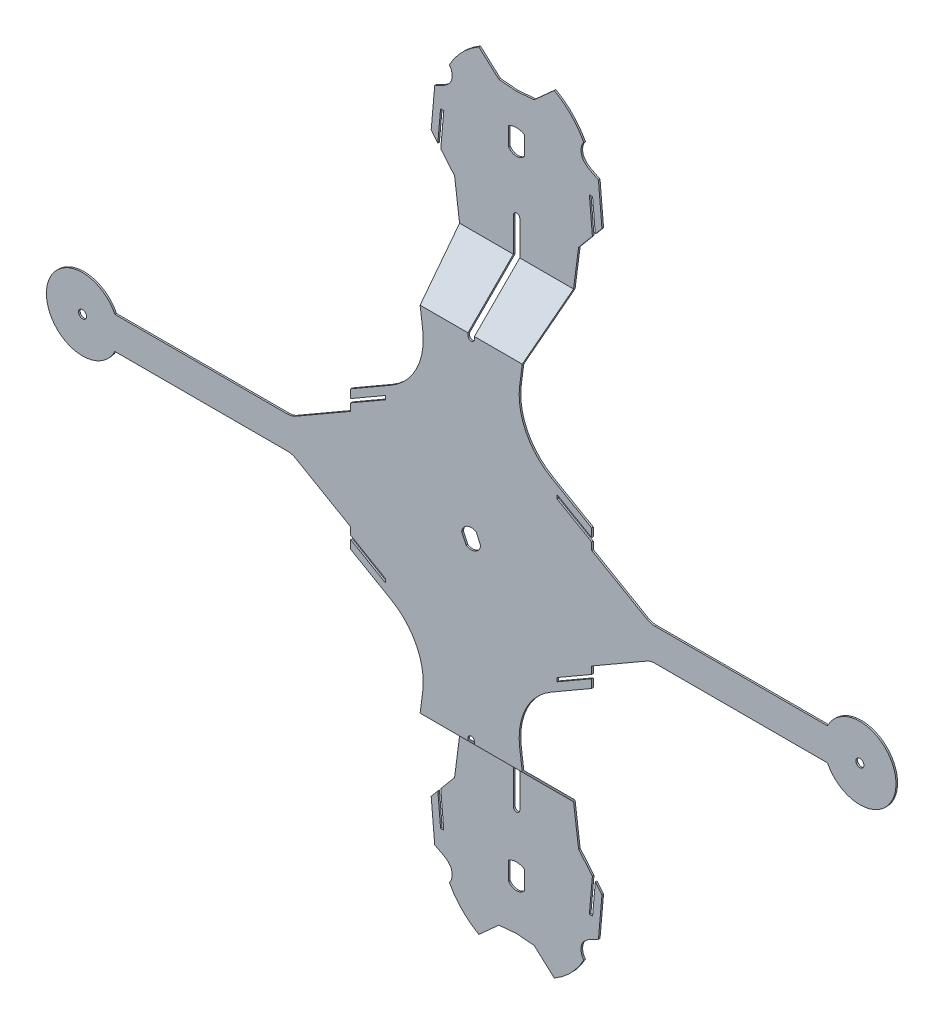
SolidWorks part; units mm, degrees
ref_plane "Alzado" through (0, 0, 0) normal (0, 0, 1) x (1, 0, 0)
ref_plane "Planta" through (0, 0, 0) normal (0, 1, 0) x (1, 0, 0)
ref_plane "Vista lateral" through (0, 0, 0) normal (1, 0, 0) x (0, 0, -1)
sketch "Croquis1" plane through (0, 0, 0) normal (1, 0, 0) x (0, 0, -1)
  line L2 (-31.6304, 0) -> (31.6304, 0) construction
  line L13 (17.5, 0) -> (17.5, 110)
  line L14 (17.5, 110) -> (45.7489, 138.2489)
  line L15 (45.7489, 138.2489) -> (45.7489, 248)
  line L16 (18.5, 0) -> (18.5, 109.5858)
  line L17 (18.5, 109.5858) -> (46.7489, 137.8347)
  line L18 (46.7489, 137.8347) -> (46.7489, 248)
  line L19 (45.7489, 248) -> (46.7489, 248)
  line L20 (45.7489, -248) -> (46.7489, -248)
  line L21 (46.7489, -137.8347) -> (46.7489, -248)
  line L22 (18.5, -109.5858) -> (46.7489, -137.8347)
  line L23 (18.5, 0) -> (18.5, -109.5858)
  line L24 (45.7489, -138.2489) -> (45.7489, -248)
  line L25 (17.5, -110) -> (45.7489, -138.2489)
  line L26 (17.5, 0) -> (17.5, -110)
  point P3 (0, 0)
  dimension "D1" = 17.5
  dimension "D2" = 110
  dimension "D3" = 45
  dimension "D4" = 39.95
  dimension "D5" = 496
  dimension "D6" = 1
extrude "Saliente-Extruir1" add sketch "Croquis1" along normal mid plane 542
sketch "Croquis5" plane through (0, 0, 0) normal (0, 0, 1) x (1, 0, 0)
  line L0 (-923.9507, 561.734) -> (-241.388, 573.6482) construction
sketch "Croquis2" plane through (0, 0, 0) normal (0, 0, 1) x (1, 0, 0)
  line L1 (0, 277.0309) -> (0, -277.0309) construction
  line L9 (-300.4496, 0) -> (300.4496, 0) construction
  line L10 (0, 108.5) -> (0, 159.5) construction
  line L11 (-2, 108.5) -> (-2, 159.5)
  line L12 (2, 108.5) -> (2, 159.5)
  line L13 (-30, 152) -> (-47.205, 172.5041) construction
  line L14 (-53.1684, 179.6111) -> (-50.9701, 204.7381)
  line L15 (-23.5, 239.2795) -> (-11, 228.0419)
  line L34 (-11, 228.0419) -> (0, 227.0795)
  line L35 (-49.0231, 174.6708) -> (-47.3316, 194.0041)
  line L36 (-47.3316, 194.0041) -> (-45.324, 194.0041)
  line L37 (-45.324, 194.0041) -> (-47.205, 172.5041)
  line L38 (-49.0231, 174.6708) -> (-53.1684, 179.6111)
  line L45 (-38.6025, 162.2521) -> (-26.75, 71.1584)
  line L79 (0, 86.6025) -> (-75, 43.3013) construction
  line L83 (-75, 43.3013) -> (-75, 38.0358)
  line L84 (-75, -43.3013) -> (0, -86.6025) construction
  line L85 (0, -86.6025) -> (75, -43.3013) construction
  line L86 (75, -43.3013) -> (75, 43.3013) construction
  line L87 (75, 43.3013) -> (0, 86.6025) construction
  line L88 (-38.6025, 162.2521) -> (-47.205, 172.5041)
  line L89 (-75, 38.0358) -> (-53.5, 50.4489)
  line L90 (-53.5, 50.4489) -> (-53.5, 48.1395)
  line L91 (-53.5, 48.1395) -> (-75, 35.7264)
  line L92 (-221.8444, 10) -> (-111.6613, 10)
  line L93 (-221.8444, -10) -> (-75, -10) construction
  line L94 (-75, 31.1664) -> (-111.6613, 10)
  line L95 (-75, 35.7264) -> (-75, -43.3013) construction
  line L96 (-75, 43.3013) -> (-26.75, 71.1584)
  line L97 (-75, 31.1664) -> (-75, 35.7264)
  line L98 (-221.8444, -10) -> (-111.6613, -10)
  line L99 (-75, -31.1664) -> (-111.6613, -10)
  line L100 (-75, -31.1664) -> (-75, -35.7264)
  line L101 (-53.5, -50.4489) -> (-53.5, -48.1395)
  line L102 (-53.5, -48.1395) -> (-75, -35.7264)
  line L103 (-75, -43.3013) -> (-75, -38.0358)
  line L104 (-75, -38.0358) -> (-53.5, -50.4489)
  line L105 (-75, -43.3013) -> (-26.75, -71.1584)
  line L106 (-38.6025, -162.2521) -> (-26.75, -71.1584)
  line L107 (-38.6025, -162.2521) -> (-47.205, -172.5041)
  line L108 (-45.324, -194.0041) -> (-47.205, -172.5041)
  line L109 (-47.3316, -194.0041) -> (-45.324, -194.0041)
  line L110 (-49.0231, -174.6708) -> (-47.3316, -194.0041)
  line L111 (-49.0231, -174.6708) -> (-53.1684, -179.6111)
  line L112 (-53.1684, -179.6111) -> (-50.9701, -204.7381)
  line L113 (-23.5, -239.2795) -> (-11, -228.0419)
  line L114 (-11, -228.0419) -> (0, -227.0795)
  line L115 (30, 152) -> (47.205, 172.5041) construction
  line L116 (11, -228.0419) -> (0, -227.0795)
  line L117 (23.5, -239.2795) -> (11, -228.0419)
  line L118 (53.1684, -179.6111) -> (50.9701, -204.7381)
  line L119 (49.0231, -174.6708) -> (53.1684, -179.6111)
  line L120 (49.0231, -174.6708) -> (47.3316, -194.0041)
  line L121 (47.3316, -194.0041) -> (45.324, -194.0041)
  line L122 (45.324, -194.0041) -> (47.205, -172.5041)
  line L123 (38.6025, -162.2521) -> (47.205, -172.5041)
  line L124 (38.6025, -162.2521) -> (26.75, -71.1584)
  line L125 (75, -43.3013) -> (26.75, -71.1584)
  line L126 (75, -38.0358) -> (53.5, -50.4489)
  line L127 (75, -43.3013) -> (75, -38.0358)
  line L128 (53.5, -48.1395) -> (75, -35.7264)
  line L129 (53.5, -50.4489) -> (53.5, -48.1395)
  line L130 (75, -31.1664) -> (75, -35.7264)
  line L131 (75, -31.1664) -> (111.6613, -10)
  line L132 (221.8444, -10) -> (111.6613, -10)
  line L133 (75, 31.1664) -> (75, 35.7264)
  line L134 (75, 43.3013) -> (26.75, 71.1584)
  line L135 (75, 31.1664) -> (111.6613, 10)
  line L136 (221.8444, 10) -> (111.6613, 10)
  line L137 (53.5, 48.1395) -> (75, 35.7264)
  line L138 (53.5, 50.4489) -> (53.5, 48.1395)
  line L139 (75, 38.0358) -> (53.5, 50.4489)
  line L140 (38.6025, 162.2521) -> (47.205, 172.5041)
  line L141 (75, 43.3013) -> (75, 38.0358)
  line L142 (38.6025, 162.2521) -> (26.75, 71.1584)
  line L143 (49.0231, 174.6708) -> (53.1684, 179.6111)
  line L144 (45.324, 194.0041) -> (47.205, 172.5041)
  line L145 (47.3316, 194.0041) -> (45.324, 194.0041)
  line L146 (49.0231, 174.6708) -> (47.3316, 194.0041)
  line L147 (11, 228.0419) -> (0, 227.0795)
  line L148 (23.5, 239.2795) -> (11, 228.0419)
  line L149 (53.1684, 179.6111) -> (50.9701, 204.7381)
  line L150 (0, -108.5) -> (0, -159.5) construction
  line L151 (-2, -108.5) -> (-2, -159.5)
  line L152 (2, -108.5) -> (2, -159.5)
  line L154 (-300.4496, 277.0309) -> (300.4496, 277.0309)
  line L155 (-300.4496, 277.0309) -> (-300.4496, -277.0309)
  line L156 (-300.4496, -277.0309) -> (300.4496, -277.0309)
  line L157 (300.4496, 277.0309) -> (300.4496, -277.0309)
  line L158 (-300.4496, 277.0309) -> (300.4496, -277.0309) construction
  line L159 (-300.4496, -277.0309) -> (300.4496, 277.0309) construction
  circle A9 centre (0, 0) radius 247.5 construction
  arc A12 (-2, 108.5) -> (2, 108.5) centre (0, 108.5) ccw
  arc A13 (2, 159.5) -> (-2, 159.5) centre (0, 159.5) ccw
  arc A14 (-41.8968, 220.3811) -> (-23.5, 239.2795) centre (0, 198) cw
  circle A15 centre (0, 198) radius 47.5 construction
  circle A16 centre (0, 0) radius 75 construction
  arc A22 (-221.8444, 10) -> (-221.8444, -10) centre (-242, 0) ccw
  arc A23 (-41.8968, -220.3811) -> (-23.5, -239.2795) centre (0, -198) ccw
  arc A24 (41.8968, -220.3811) -> (23.5, -239.2795) centre (0, -198) cw
  arc A25 (221.8444, 10) -> (221.8444, -10) centre (242, 0) cw
  arc A26 (41.8968, 220.3811) -> (23.5, 239.2795) centre (0, 198) ccw
  arc A27 (-2, -108.5) -> (2, -108.5) centre (0, -108.5) cw
  arc A28 (2, -159.5) -> (-2, -159.5) centre (0, -159.5) cw
  spline S0 degree 3 poles (-50.9701, 204.7381) (-47.793, 206.2687) (-40.7871, 209.0246) (-39.8831, 216.4184) (-40.7368, 219.1761) (-41.8968, 220.3811) knots 0 0 0 0 0.610721 0.773573 1 1 1 1
  spline S1 degree 3 poles (-50.9701, -204.7381) (-47.793, -206.2687) (-40.7871, -209.0246) (-39.8831, -216.4184) (-40.7368, -219.1761) (-41.8968, -220.3811) knots 0 0 0 0 0.610721 0.773573 1 1 1 1
  spline S2 degree 3 poles (50.9701, -204.7381) (47.793, -206.2687) (40.7871, -209.0246) (39.8831, -216.4184) (40.7368, -219.1761) (41.8968, -220.3811) knots 0 0 0 0 0.610721 0.773573 1 1 1 1
  spline S3 degree 3 poles (50.9701, 204.7381) (47.793, 206.2687) (40.7871, 209.0246) (39.8831, 216.4184) (40.7368, 219.1761) (41.8968, 220.3811) knots 0 0 0 0 0.610721 0.773573 1 1 1 1
  point P6 (0, 0)
  point P7 (0, 0)
  point P15 (0, 134)
  point P58 (-53.5, 49.2942)
  point P126 (0, -134)
  dimension "D1" = 495
  dimension "D3" = 242
  dimension "D9" = 198
  dimension "D4" = 150
  dimension "D6" = 45
  dimension "D10" = 134
  dimension "D14" = 152
  dimension "D5" = 95
  dimension "D23" = 21.6
  dimension "D24" = 4.56
  dimension "D7" = 51
  dimension "D8" = 4
  dimension "D11" = 30
  dimension "D12" = 2
  dimension "D13" = 50
  dimension "D15" = 25.1271
  dimension "D16" = 5
  dimension "D17" = 179.6111
  dimension "D18" = 5
  dimension "D19" = 11
  dimension "D20" = 23.5
  dimension "D21" = 12.2
  dimension "D22" = 21.5
  dimension "D25" = 2
  dimension "D26" = 20
  dimension "D27" = 4.56
  dimension "D28" = 53.5
  dimension "D29" = 21.5
sketch "Croquis4" plane through (0, 0, 0) normal (0, 0, 1) x (1, 0, 0)
  line L0 (-326.6263, 0) -> (326.6263, 0) construction
  line L1 (0, 278.5393) -> (0, -278.5393) construction
  line L2 (-5, -194.6834) -> (5, -201.3166) construction
  line L3 (-5, 201.3166) -> (5, 201.3166) construction
  line L4 (-5, 201.3166) -> (-5, 194.6834)
  line L5 (-5, 194.6834) -> (5, 194.6834) construction
  line L6 (5, 201.3166) -> (5, 194.6834)
  line L7 (-5, 201.3166) -> (5, 194.6834) construction
  line L8 (-5, 194.6834) -> (5, 201.3166) construction
  line L9 (-5, -201.3166) -> (5, -194.6834) construction
  line L10 (-5, -194.6834) -> (5, -194.6834) construction
  line L11 (-5, -201.3166) -> (5, -201.3166) construction
  line L12 (5, -201.3166) -> (5, -194.6834)
  line L13 (-5, -201.3166) -> (-5, -194.6834)
  line L20 (-5, 201.3166) -> (-5, 206.0777)
  line L21 (5, 201.3166) -> (5, 206.0777)
  line L26 (-5.9332, 0.8928) -> (3.1299, 5.119) construction
  line L27 (-5.9332, 0.8928) -> (-3.1299, -5.119)
  line L28 (3.1299, 5.119) -> (5.9332, -0.8928)
  line L29 (-3.1299, -5.119) -> (5.9332, -0.8928) construction
  line L30 (0, 0) -> (-1.4017, 3.0059) construction
  line L31 (-8.5, 202.2426) -> (-8.5, 193.7574) construction
  line L32 (8.5, 202.2426) -> (8.5, 193.7574) construction
  line L33 (-5, -194.6834) -> (-5, -189.9223)
  line L34 (5, -194.6834) -> (5, -189.9223)
  line L38 (-8.5, -202.2426) -> (-8.5, -193.7574) construction
  line L39 (8.5, -202.2426) -> (8.5, -193.7574) construction
  arc A0 (-5, 194.6834) -> (5, 194.6834) centre (0, 198) ccw
  arc A1 (-3.1299, -5.119) -> (5.9332, -0.8928) centre (0, 0) ccw
  arc A4 (5, 201.3166) -> (-5, 201.3166) centre (0, 198) ccw construction
  arc A5 (5, -201.3166) -> (-5, -201.3166) centre (0, -198) cw
  arc A6 (-5, -194.6834) -> (5, -194.6834) centre (0, -198) cw construction
  circle A7 centre (-242, 0) radius 2.5
  arc A10 (3.1299, 5.119) -> (-5.9332, 0.8928) centre (0, 0) ccw
  circle A11 centre (242, 0) radius 2.5
  arc A12 (5, 206.0777) -> (-5, 206.0777) centre (0, 198) ccw
  arc A14 (8.5, 202.2426) -> (-8.5, 202.2426) centre (0, 198) ccw construction
  arc A15 (-8.5, 193.7574) -> (8.5, 193.7574) centre (0, 198) ccw construction
  arc A16 (-5, -189.9223) -> (5, -189.9223) centre (0, -198) cw
  arc A18 (-8.5, -193.7574) -> (8.5, -193.7574) centre (0, -198) cw construction
  arc A19 (8.5, -202.2426) -> (-8.5, -202.2426) centre (0, -198) cw construction
  point P4 (0, 0)
  point P8 (0, 0)
  dimension "D3" = 242
  dimension "D4" = 10
  dimension "D5" = 12
  dimension "D6" = 12
  dimension "D2" = 5
  dimension "D1" = 198
  dimension "D7" = 3.5
  dimension "D8" = 10
  dimension "D9" = 25
  dimension "D10" = 3.5
extrude "Cortar-Extruir9" cut sketch "Croquis4" against normal through all both and the other way through all
extrude "Cortar-Extruir10" cut sketch "Croquis2" against normal through all both and the other way through all contours L157 L154 L155 L156 S3 L149 L143 L146 L145 L144 L140 L142 L134 L141 L139 L138 L137 L133 L135 L136 A25 L132 L131 L130 L128 L129 L126 L127 L125 L124 L123 L122 L121 L120 L119 L118 S2 A24 L117 L116 L114 L113 A23 S1 L112 L111 L110 L109 L108 L107 | A28 L152 A27 L151 | L12 A13 L11 A12 region at (0, -134, 0) region at (0, 268.8574, 0)
fillet "Redondeo1" radius 40 4 edges at (26.75, -71.1584, -18) (-26.75, -71.1584, -18) (-26.75, 71.1584, -18) (26.75, 71.1584, -18)
fillet "Redondeo2" radius 10 4 edges at (-111.6613, -10, -18) (-111.6613, 10, -18) (111.6613, -10, -18) (111.6613, 10, -18)
